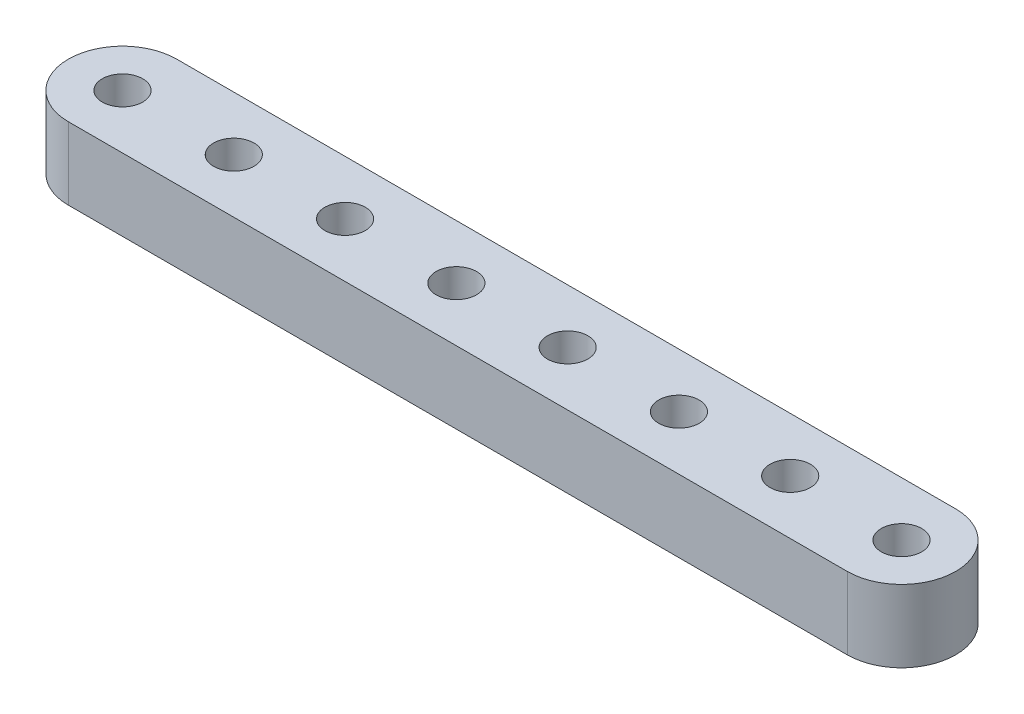
SolidWorks part; units mm, degrees
ref_plane "Front Plane" through (0, 0, 0) normal (0, 0, 1) x (1, 0, 0)
ref_plane "Top Plane" through (0, 0, 0) normal (0, 1, 0) x (1, 0, 0)
ref_plane "Right Plane" through (0, 0, 0) normal (1, 0, 0) x (0, 0, -1)
ref_plane "Plane1" through (0, 0, 0) normal (0, -1, 0) x (1, 0, 0)
sketch "Sketch1" plane through (0, 0, 0) normal (0, -1, 0) x (1, 0, 0)
  line L0 (-39.116, -4.7625) -> (39.116, -4.7625)
  line L1 (39.116, 4.7625) -> (-39.116, 4.7625)
  arc A0 (39.116, -4.7625) -> (39.116, 4.7625) centre (39.116, 0) ccw
  arc A1 (-39.116, 4.7625) -> (-39.116, -4.7625) centre (-39.116, 0) ccw
  circle A2 centre (39.116, 0) radius 1.778
  circle A3 centre (29.337, 0) radius 1.778
  circle A4 centre (19.558, 0) radius 1.778
  circle A5 centre (9.779, 0) radius 1.778
  circle A6 centre (0, 0) radius 1.778
  circle A7 centre (-9.779, 0) radius 1.778
  circle A8 centre (-19.558, 0) radius 1.778
  circle A9 centre (-29.337, 0) radius 1.778
  circle A10 centre (-39.116, 0) radius 1.778
extrude "Boss-Extrude1" add sketch "Sketch1" against normal blind 6.35
sketch "Sketch2" plane through (0, 6.35, 0) normal (0, 1, 0) x (1, 0, 0)
  line L0 (39.116, -4.7625) -> (-39.116, -4.7625) construction
  line L1 (-34.0995, -4.7625) -> (-49.2255, -4.7625)
  line L2 (-34.0995, -4.7625) -> (-34.0995, 4.9484)
  line L3 (-34.0995, 4.9484) -> (-49.2255, 4.9484)
  line L4 (-49.2255, -4.7625) -> (-49.2255, 4.9484)
  circle A0 centre (-29.337, 0) radius 1.778 construction
  dimension "D1" = 4.7625
extrude "Cut-Extrude1" cut sketch "Sketch2" against normal through all both and the other way through all
fillet "Fillet1" radius 4.7625 2 edges at (-34.0995, 3.175, -4.7625) (-34.0995, 3.175, 4.7625)
